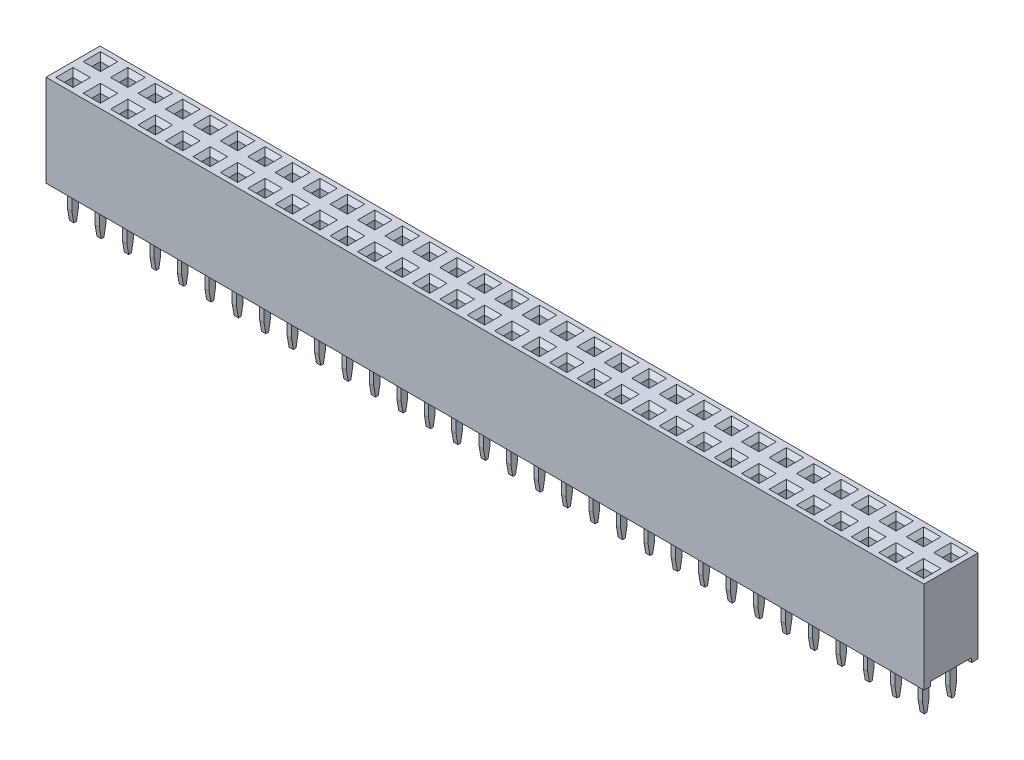
SolidWorks part; units mm, degrees
ref_plane "Спереди" through (0, 0, 0) normal (0, 0, 1) x (1, 0, 0)
ref_plane "Сверху" through (0, 0, 0) normal (0, 1, 0) x (1, 0, 0)
ref_plane "Справа" through (0, 0, 0) normal (1, 0, 0) x (0, 0, -1)
sketch "Эскиз1" plane through (0, 0, 0) normal (1, 0, 0) x (0, 0, -1)
  line L0 (0, 0) -> (0, 11245.8688) construction
  line L1 (0, 0.4) -> (1.9, 0.4)
  line L2 (1.9, 0.4) -> (1.9, 0)
  line L3 (1.9, 0) -> (2.5, 0)
  line L4 (2.5, 0) -> (2.5, 8.5)
  line L5 (2.5, 8.5) -> (0, 8.5)
  line L6 (0, 8.5) -> (0, 0.4)
  dimension "D1" = 5
  dimension "D2" = 8.5
  dimension "D3" = 0.6
  dimension "D4" = 0.4
extrude "Бобышка-Вытянуть1" add sketch "Эскиз1" along normal mid plane 2.54
sketch "Эскиз2" plane through (0, 0, 0) normal (1, 0, 0) x (0, 0, -1)
  line L0 (0.97, 0.4) -> (0.97, -2)
  line L1 (0, 0.4) -> (1.9, 0.4) construction
  line L2 (0.97, -2) -> (1.1463, -3)
  line L3 (1.1463, -3) -> (1.3937, -3)
  line L5 (1.57, 0.4) -> (0.97, 0.4)
  line L6 (1.27, -2.9705) -> (1.27, -50002.9705) construction
  line L7 (1.57, -2) -> (1.3937, -3)
  line L8 (1.57, 0.4) -> (1.57, -2)
  line L9 (1.9, 0) -> (2.5, 0) construction
  dimension "D1" = 0.6
  dimension "D2" = 10
  dimension "D3" = 1
  dimension "D4" = 3
  dimension "D5" = 1.27
extrude "Бобышка-Вытянуть2" add sketch "Эскиз2" along normal mid plane 0.4
sketch "Эскиз3" plane through (0, 8.5, 0) normal (0, 1, 0) x (1, 0, 0)
  line L1 (-0.4, 1.67) -> (0.4, 1.67)
  line L2 (-0.4, 1.67) -> (-0.4, 0.87)
  line L3 (-0.4, 0.87) -> (0.4, 0.87)
  line L4 (0.4, 1.67) -> (0.4, 0.87)
  line L5 (-0.4, 1.67) -> (0.4, 0.87) construction
  line L6 (-0.4, 0.87) -> (0.4, 1.67) construction
  point P0 (0, 1.27)
  point P5 (0, 0)
  dimension "D1" = 0.8
  dimension "D2" = 1.27
extrude "Вырез-Вытянуть1" cut sketch "Эскиз3" against normal blind 7
chamfer "Фаска1" distance 0.4 angle 45 4 edges at (0.4, 8.5, -1.27) (0, 8.5, -0.87) (0, 8.5, -1.67) (-0.4, 8.5, -1.27)
mirror "Зеркальное отражение1" about plane through (1.27, 8.5, 0) normal (0, 0, -1) of bodies 105
pattern_linear "Линейный массив1" count 32 spacing 2.54 along (1, 0, 0) of bodies 106
combine bodies "Соединить1" operation type add bodies to combine 106 116 133 111 128 123 118 135 113 130 108 125 120 137 115 132 110 127 122 117 134 112 129 107 124 119 136 114 131 109 126 121
